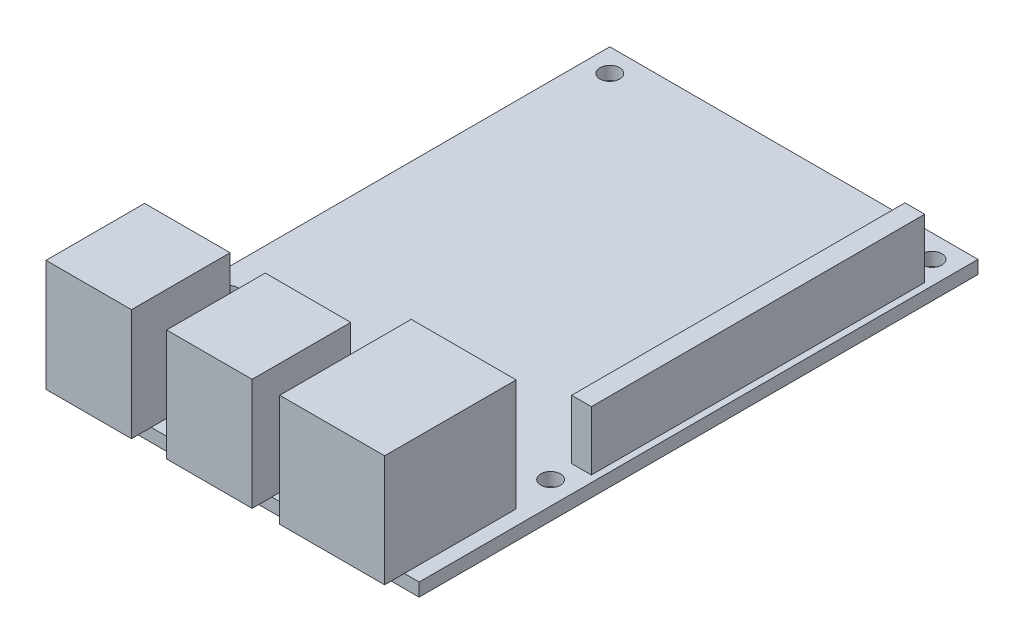
SolidWorks part; units mm, degrees
ref_plane "Front Plane" through (0, 0, 0) normal (0, 0, 1) x (1, 0, 0)
ref_plane "Top Plane" through (0, 0, 0) normal (0, 1, 0) x (1, 0, 0)
ref_plane "Right Plane" through (0, 0, 0) normal (1, 0, 0) x (0, 0, -1)
sketch "Sketch1" plane through (0, 0, 0) normal (0, 1, 0) x (1, 0, 0)
  line L1 (-28, -42.5) -> (28, -42.5)
  line L2 (-28, -42.5) -> (-28, 42.5)
  line L3 (-28, 42.5) -> (28, 42.5)
  line L4 (28, -42.5) -> (28, 42.5)
  line L5 (-28, -42.5) -> (28, 42.5) construction
  line L6 (-28, 42.5) -> (28, -42.5) construction
  line L7 (-24.5, 39) -> (24.5, 39) construction
  line L8 (-24.5, 39) -> (-24.5, -19) construction
  line L9 (-24.5, -19) -> (24.5, -19) construction
  line L10 (24.5, 39) -> (24.5, -19) construction
  circle A0 centre (-24.5, 39) radius 1.5
  circle A1 centre (24.5, 39) radius 1.5
  circle A2 centre (-24.5, -19) radius 1.5
  circle A3 centre (24.5, -19) radius 1.5
  point P0 (0, 0)
  point P10 (0, 39)
  dimension "D6" = 3
  dimension "D1" = 56
  dimension "D2" = 85
  dimension "D3" = 49
  dimension "D4" = 58
  dimension "D5" = 3.5
extrude "Boss-Extrude1" add sketch "Sketch1" along normal blind 2
sketch "Sketch2" plane through (0, 2, 0) normal (0, 1, 0) x (1, 0, 0)
  line L0 (28, 42.5) -> (-28, 42.5) construction
  line L1 (27, 35.4) -> (24, 35.4)
  line L2 (27, 35.4) -> (27, -15.3)
  line L3 (27, -15.3) -> (24, -15.3)
  line L4 (24, 35.4) -> (24, -15.3)
  line L5 (-28, -42.5) -> (28, -42.5) construction
  line L6 (28, -42.5) -> (28, 42.5) construction
  point P8 (0, 0)
  dimension "D1" = 7.1
  dimension "D2" = 27.2
  dimension "D3" = 3
  dimension "D4" = 1
extrude "Boss-Extrude2" add sketch "Sketch2" along normal blind 9
sketch "Sketch3" plane through (0, 2, 0) normal (0, 1, 0) x (1, 0, 0)
  line L0 (28, -42.5) -> (28, 42.5) construction
  line L1 (-25.75, -30.5) -> (-12.75, -30.5)
  line L2 (-25.75, -30.5) -> (-25.75, -45.5)
  line L3 (-25.75, -45.5) -> (-12.75, -45.5)
  line L4 (-12.75, -30.5) -> (-12.75, -45.5)
  line L5 (-7.4, -30.5) -> (5.6, -30.5)
  line L6 (-7.4, -30.5) -> (-7.4, -45.5)
  line L7 (-7.4, -45.5) -> (5.6, -45.5)
  line L8 (5.6, -30.5) -> (5.6, -45.5)
  line L9 (9.8, -25.5) -> (25.75, -25.5)
  line L10 (9.8, -25.5) -> (9.8, -45.5)
  line L11 (9.8, -45.5) -> (25.75, -45.5)
  line L12 (25.75, -25.5) -> (25.75, -45.5)
  line L13 (-28, 42.5) -> (-28, -42.5) construction
  line L14 (-28, -42.5) -> (28, -42.5) construction
  point P12 (18.7864, -44.7659)
  point P17 (-14.7081, -46.4918)
  point P18 (9.8, -47.0414)
  point P19 (2.6, -48.013)
  dimension "D1" = 2.25
  dimension "D2" = 2.25
  dimension "D3" = 20.6
  dimension "D4" = 37.8
  dimension "D5" = 13
  dimension "D6" = 15
  dimension "D7" = 20
  dimension "D8" = 3
extrude "Boss-Extrude3" add sketch "Sketch3" along normal blind 17
